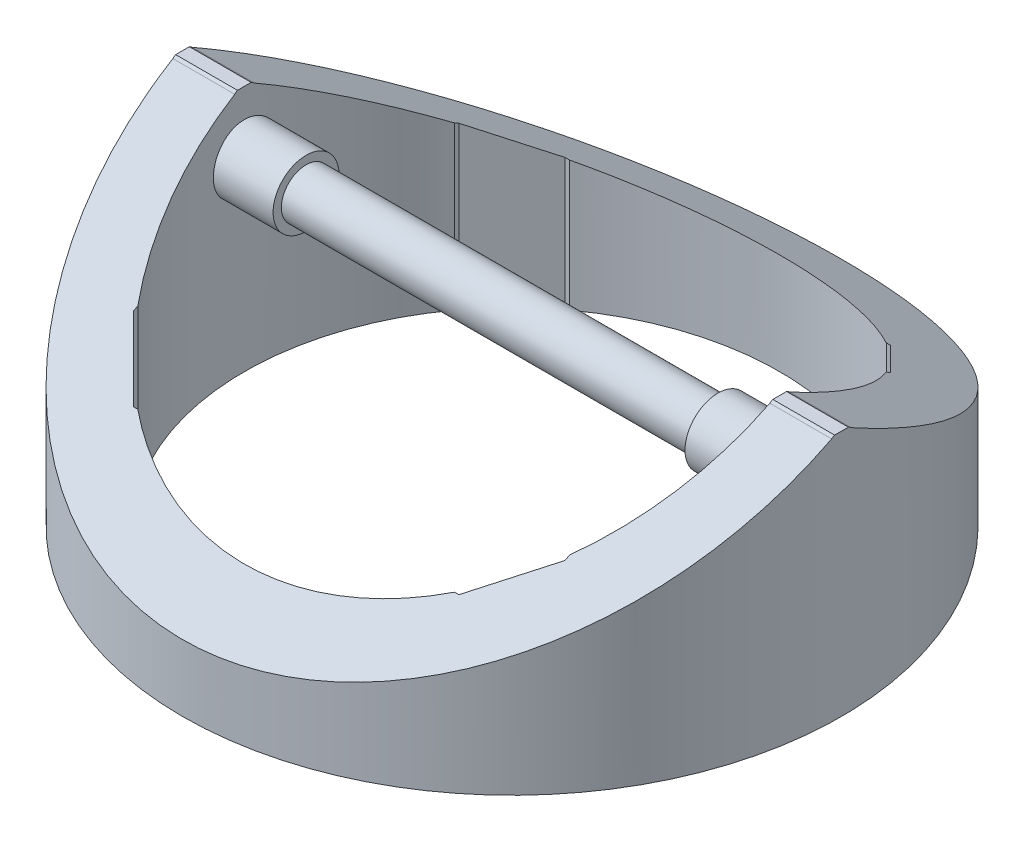
SolidWorks part; units mm, degrees
material "Commercialement pur CP-Ti UNS R50400 (SS)"
ref_plane "Plan de face" through (0, 0, 0) normal (0, 0, 1) x (1, 0, 0)
ref_plane "Plan de dessus" through (0, 0, 0) normal (0, 1, 0) x (1, 0, 0)
ref_plane "Plan de droite" through (0, 0, 0) normal (1, 0, 0) x (0, 0, -1)
sketch "Esquisse2" plane through (0, 0, 0) normal (0, 1, 0) x (1, 0, 0)
  line L0 (-262.028, 197.5914) -> (-197.5914, 262.028)
  line L5 (-262.028, -197.5914) -> (-262.028, 197.5914)
  line L6 (197.5914, -262.028) -> (-197.5914, -262.028)
  line L7 (197.5914, -262.028) -> (262.028, -197.5914)
  line L8 (-262.028, -197.5914) -> (-197.5914, -262.028)
  line L9 (197.5914, 262.028) -> (262.028, 197.5914)
  line L10 (197.5914, 262.028) -> (-197.5914, 262.028)
  line L11 (229.8097, 229.8097) -> (-229.8097, -229.8097) construction
  line L12 (229.8097, -229.8097) -> (-229.8097, 229.8097) construction
  line L13 (262.028, -197.5914) -> (262.028, 197.5914)
  circle A0 centre (0, 0) radius 400
  circle A1 centre (0, 0) radius 325
  dimension "D1" = 800
  dimension "D2" = 650
extrude "Boss.-Extru.1" add sketch "Esquisse2" along normal blind 300 contours A0 L13 L7 L6 L8 L5 L0 L10 L9 region at (-388.6863, 0, 0)
sketch "Esquisse3" plane through (0, 0, 0) normal (1, 0, 0) x (0, 0, -1)
  line L0 (0, 300) -> (0, 0) construction
  line L2 (-400, 150) -> (400, 150) construction
  line L3 (-400, 300) -> (-400, 0) construction
  line L4 (400, 0) -> (400, 300) construction
  line L5 (-15, 150) -> (-15, 290)
  line L6 (15, 150) -> (15, 290)
  line L8 (-4.1667, 300.8333) -> (4.1667, 300.8333)
  line L9 (-400, 80.8333) -> (-400, 300.8333)
  line L10 (-400, 300.8333) -> (-4.1667, 300.8333)
  line L11 (400, 80.8333) -> (400, 300.8333)
  line L12 (400, 300.8333) -> (4.1667, 300.8333)
  line L13 (-400, 80.8333) -> (-11.827, 297.6603)
  line L14 (400, 80.8333) -> (11.827, 297.6603)
  line L15 (-4.1667, 300.8333) -> (-400, 300.8333) construction
  line L16 (4.1667, 300.8333) -> (400, 300.8333) construction
  arc A0 (-15, 290) -> (-4.1667, 300.8333) centre (-4.1667, 290) cw
  arc A1 (15, 290) -> (4.1667, 300.8333) centre (4.1667, 290) ccw
  dimension "D1" = 10
  dimension "D2" = 15
  dimension "D3" = 15
  dimension "D5" = 220
extrude "Enlèv. mat.-Extru.1" cut sketch "Esquisse3" against normal blind 575 contours L13 A0 L10 L9 | A1 L14 L11 L12 region at (0, 227.4976, -268.7242) region at (0, 227.4976, 268.7242)
extrude "Enlèv. mat.-Extru.2" cut sketch "Esquisse3<3>" along normal blind 705 contours L13 A0 L10 L9 | A1 L14 L11 L12 region at (0, 227.4976, -268.7242) region at (0, 227.4976, 268.7242)
sketch "Esquisse3<3>" plane through (0, 0, 0) normal (1, 0, 0) x (0, 0, -1) same geometry as "Esquisse3"
sketch "Esquisse9" plane through (0, 0, 0) normal (1, 0, 0) x (0, 0, -1)
  line L0 (0, 300) -> (0, 0) construction
  line L1 (8.3333, 300) -> (-8.3333, 300) construction
  circle A0 centre (0, 225) radius 40
  dimension "D1" = 80
  dimension "D2" = 75
extrude "Boss.-Extru.10" add sketch "Esquisse9" along normal blind 350
extrude "Boss.-Extru.11" add sketch "Esquisse9<4>" against normal blind 350
sketch "Esquisse9<4>" plane through (0, 0, 0) normal (1, 0, 0) x (0, 0, -1) same geometry as "Esquisse9"
sketch "Esquisse10" plane through (0, 0, 0) normal (1, 0, 0) x (0, 0, -1)
  line L0 (0, 300) -> (0, 0) construction
  line L1 (8.3333, 300) -> (-8.3333, 300) construction
  circle A0 centre (0, 225) radius 30
  circle A1 centre (0, 225) radius 40
  dimension "D2" = 60
  dimension "D3" = 80
  dimension "D1" = 75
extrude "Enlèv. mat.-Extru.3" cut sketch "Esquisse10" against normal blind 250
extrude "Enlèv. mat.-Extru.4" cut sketch "Esquisse10<2>" along normal blind 250
sketch "Esquisse10<2>" plane through (0, 0, 0) normal (1, 0, 0) x (0, 0, -1) same geometry as "Esquisse10"
